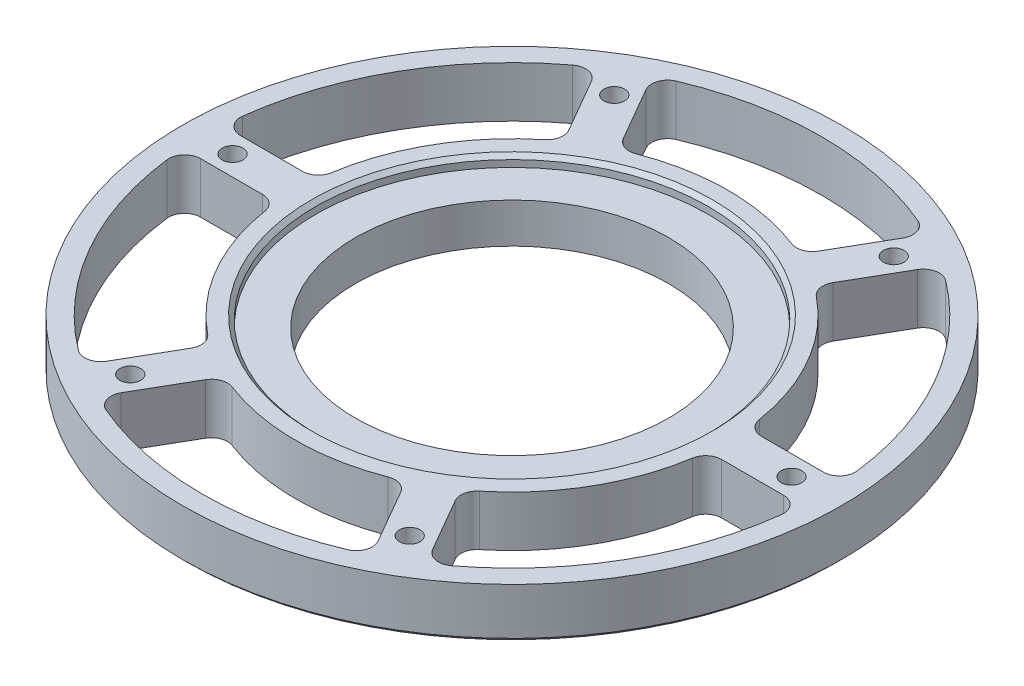
SolidWorks part; units mm, degrees
material "6061-T6 (SS)"
ref_plane "Front Plane" through (0, 0, 0) normal (0, 0, 1) x (1, 0, 0)
ref_plane "Top Plane" through (0, 0, 0) normal (0, 1, 0) x (1, 0, 0)
ref_plane "Right Plane" through (0, 0, 0) normal (1, 0, 0) x (0, 0, -1)
sketch "Sketch2" plane through (0, 0, 0) normal (1, 0, 0) x (0, 0, -1)
  line L0 (-39.2125, 0) -> (-82.55, 0)
  line L1 (-82.55, 0) -> (-82.55, 12.7)
  line L2 (-82.55, 12.7) -> (-49.2125, 12.7)
  line L3 (-49.2125, 12.7) -> (-49.2125, 10)
  line L4 (-49.2125, 10) -> (-39.2125, 10)
  line L5 (-39.2125, 10) -> (-39.2125, 0)
  dimension "D1" = 82.55
  dimension "D2" = 12.7
  dimension "D4" = 49.2125
  dimension "D5" = 10
  dimension "D3" = 10
ref_axis "Axis1" through (0, -0.635, 0) along (0, 1, 0)
revolve "Revolve1" add sketch "Sketch2" angle 360 about axis through (0, -0.635, 0) along (0, 1, 0)
hole_wizard "#6 (0.204) Diameter Hole1" positions "Sketch6" profile "Sketch7" hole size "#6" standard "ANSI Inch" end condition through all
sketch "Sketch6" plane through (0, 12.7, 0) normal (0, 1, 0) x (1, 0, 0)
  line L0 (0, 0) -> (-69.8201, 120.932) construction
  line L2 (0, 0) -> (0, 109.0908) construction
  point P0 (-35, 60.6218)
  dimension "D1" = 30
  dimension "D2" = 70
sketch "Sketch7" plane through (-35, 12.7, -60.6218) normal (1, 0, 0) x (0, 0, 1)
  line L0 (0, 0) -> (0, 12.7)
  line L1 (0, 12.7) -> (2.5908, 12.7)
  line L2 (2.5908, 12.7) -> (2.5908, 0)
  line L5 (2.5908, 0) -> (0, 0)
  line L11 (0, -6.35) -> (0, 107.95) construction
  dimension "Thru Hole Dia." = 5.1816
  dimension "Thru Hole Depth" = 12.7
pattern_circular "CirPattern3" count 6 over 360 about axis through (0, -0.635, 0) along (0, 1, 0) of "#6 (0.204) Diameter Hole1"
sketch "Sketch8" plane through (0, 12.7, 0) normal (0, 1, 0) x (1, 0, 0)
  line L0 (-34.3642, 69.5205) -> (-22.6606, 49.2493)
  line L1 (34.3642, 69.5205) -> (22.6606, 49.2493)
  line L2 (0, 0) -> (-35, 60.6218) construction
  line L4 (0, 0) -> (0, 93.9995) construction
  arc A0 (-22.6606, 49.2493) -> (22.6606, 49.2493) centre (0, 0) cw
  arc A1 (-34.3642, 69.5205) -> (34.3642, 69.5205) centre (0, 0) cw
  circle A2 centre (0, 0) radius 49.2125 construction
  circle A3 centre (0, 0) radius 82.55 construction
  dimension "D1" = 5
  dimension "D2" = 5
  dimension "D3" = 5
extrude "Cut-Extrude1" cut sketch "Sketch8" against normal through all
fillet "Fillet1" radius 4 4 edges at (34.3642, 6.35, -69.5205) (22.6606, 6.35, -49.2493) (-34.3642, 6.35, -69.5205) (-22.6606, 6.35, -49.2493)
pattern_circular "CirPattern4" count 6 over 360 about axis through (0, -0.635, 0) along (0, 1, 0) of "Cut-Extrude1", "Fillet1"
chamfer "Chamfer1" distance 1 angle 45 1 edges at (0, 12.7, -49.2125)
chamfer "Chamfer2" distance 1 angle 45 1 edges at (0, 0, -82.55)
equation "\"TubeDiameter\" = 6.500in"
equation "\"D1@Sketch2\"=\"TubeDiameter\"/2"
